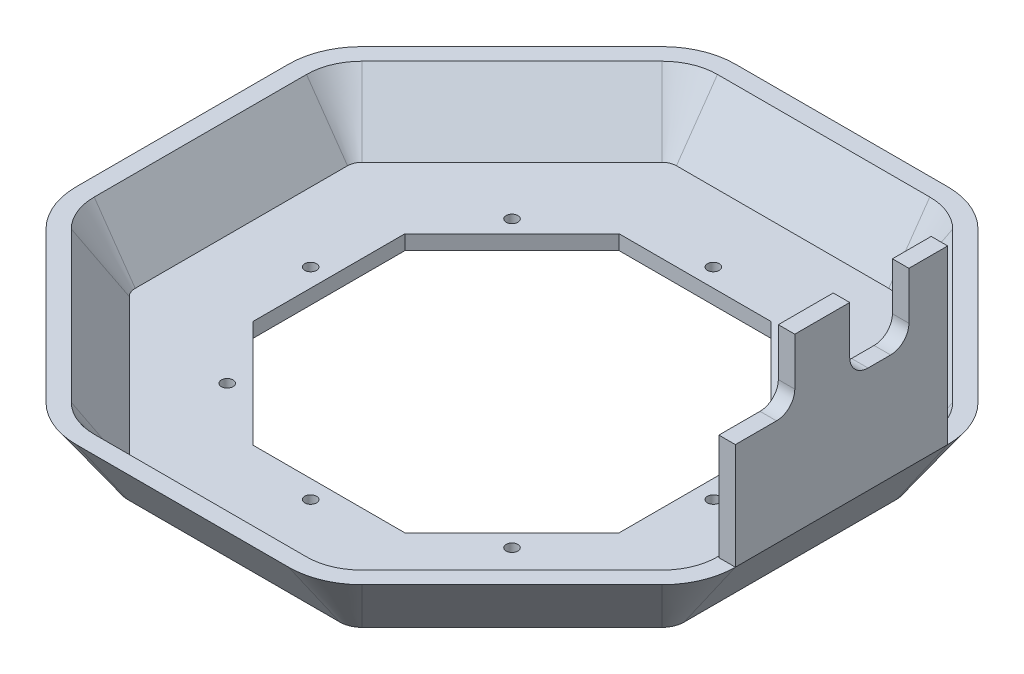
SolidWorks part; units mm, degrees
ref_plane "Front Plane" through (0, 0, 0) normal (0, 0, 1) x (1, 0, 0)
ref_plane "Top Plane" through (0, 0, 0) normal (0, 1, 0) x (1, 0, 0)
ref_plane "Right Plane" through (0, 0, 0) normal (1, 0, 0) x (0, 0, -1)
sketch "Sketch1" plane through (0, 0, 0) normal (0, 1, 0) x (1, 0, 0)
  line L1 (90, -28.9949) -> (90, 28.9949)
  line L2 (84.1421, 43.1371) -> (43.1371, 84.1421)
  line L3 (28.9949, 90) -> (-28.9949, 90)
  line L4 (-43.1371, 84.1421) -> (-84.1421, 43.1371)
  line L5 (-90, 28.9949) -> (-90, -28.9949)
  line L6 (-84.1421, -43.1371) -> (-43.1371, -84.1421)
  line L7 (-28.9949, -90) -> (28.9949, -90)
  line L8 (43.1371, -84.1421) -> (84.1421, -43.1371)
  circle A0 centre (0, 0) radius 90 construction
  arc A1 (-90, -28.9949) -> (-84.1421, -43.1371) centre (-70, -28.9949) ccw
  arc A2 (-43.1371, -84.1421) -> (-28.9949, -90) centre (-28.9949, -70) ccw
  arc A3 (28.9949, -90) -> (43.1371, -84.1421) centre (28.9949, -70) ccw
  arc A4 (90, -28.9949) -> (84.1421, -43.1371) centre (70, -28.9949) cw
  arc A5 (90, 28.9949) -> (84.1421, 43.1371) centre (70, 28.9949) ccw
  arc A6 (43.1371, 84.1421) -> (28.9949, 90) centre (28.9949, 70) ccw
  arc A7 (-28.9949, 90) -> (-43.1371, 84.1421) centre (-28.9949, 70) ccw
  arc A8 (-84.1421, 43.1371) -> (-90, 28.9949) centre (-70, 28.9949) ccw
  dimension "D1" = 180
  dimension "D2" = 20
extrude "Initial extrude" add sketch "Sketch1" along normal blind 20
chamfer "Top chamfer" distance 20 angle 35 16 edges at (0, 20, 90) (-63.6396, 20, 63.6396) (-90, 20, 0) (-63.6396, 20, -63.6396) (0, 20, -90) (63.6396, 20, -63.6396) (90, 20, 0) (63.6396, 20, 63.6396) (-88.4776, 20, -36.6486) (-36.6486, 20, -88.4776) (36.6486, 20, -88.4776) (88.4776, 20, -36.6486) (88.4776, 20, 36.6486) (36.6486, 20, 88.4776) (-36.6486, 20, 88.4776) (-88.4776, 20, 36.6486) first distance on face at (0, 10, 90) first distance on face at (-63.6396, 10, 63.6396) first distance on face at (-90, 10, 0) first distance on face at (-63.6396, 10, -63.6396) first distance on face at (0, 10, -90) first distance on face at (63.6396, 10, -63.6396) first distance on face at (90, 10, 0) first distance on face at (63.6396, 10, 63.6396) first distance on face at (-87.7743, 10, -36.3573) first distance on face at (-36.3573, 10, -87.7743) first distance on face at (36.3573, 10, -87.7743) first distance on face at (87.7743, 10, -36.3573) first distance on face at (87.7743, 10, 36.3573) first distance on face at (36.3573, 10, 87.7743) first distance on face at (-36.3573, 10, 87.7743) first distance on face at (-87.7743, 10, 36.3573)
shell "Top shell" thickness 4 removed face at (0, 0, 0)
sketch "Sketch2" plane through (0, 20, 0) normal (0, 1, 0) x (1, 0, 0)
  line L1 (20.7107, 50) -> (-20.7107, 50)
  line L2 (-20.7107, 50) -> (-50, 20.7107)
  line L3 (-50, 20.7107) -> (-50, -20.7107)
  line L4 (-50, -20.7107) -> (-20.7107, -50)
  line L5 (-20.7107, -50) -> (20.7107, -50)
  line L6 (20.7107, -50) -> (50, -20.7107)
  line L7 (50, -20.7107) -> (50, 20.7107)
  line L8 (50, 20.7107) -> (20.7107, 50)
  circle A0 centre (0, 0) radius 50 construction
  dimension "D1" = 100
extrude "Interior hex hole" cut sketch "Sketch2" against normal through all
sketch "Sketch3" plane through (0, 16, 0) normal (0, -1, 0) x (1, 0, 0)
  line L0 (-50, -20.7107) -> (-50, 20.7107) construction
  circle A0 centre (-55, 0) radius 1.6
  circle A1 centre (-38.8909, 38.8909) radius 1.6
  circle A2 centre (0, 55) radius 1.6
  circle A3 centre (38.8909, 38.8909) radius 1.6
  circle A4 centre (55, 0) radius 1.6
  circle A5 centre (38.8909, -38.8909) radius 1.6
  circle A6 centre (0, -55) radius 1.6
  circle A7 centre (-38.8909, -38.8909) radius 1.6
  point P22 (0, 0)
  dimension "D1" = 3.2
  dimension "D2" = 5
  dimension "D3" = 8
extrude "Top screw holes" cut sketch "Sketch3" against normal through all
ref_plane "Plane1" through (0, 0, 0) normal (0, 0, -1) x (-1, 0, 0)
sketch "Sketch6" plane through (0, 0, 0) normal (0, -1, 0) x (1, 0, 0)
  line L0 (-90, -28.9949) -> (-90, 28.9949) construction
  line L1 (-90, -28.9949) -> (-85.5, -28.9949)
  line L2 (-90, -28.9949) -> (-90, 28.9949)
  line L3 (-90, 28.9949) -> (-85.5, 28.9949)
  line L4 (-85.5, -28.9949) -> (-85.5, 28.9949)
  dimension "D1" = 4.5
extrude "Boss-Extrude2" add sketch "Sketch6" along normal blind 29
sketch "Sketch7" plane through (0, -29, 0) normal (0, -1, 0) x (1, 0, 0)
  line L0 (-90, 28.9949) -> (-90, -28.9949) construction
  line L1 (-90, -2.2382) -> (-85.5, -2.2382)
  line L2 (-90, -2.2382) -> (-90, 12.7618)
  line L3 (-90, 12.7618) -> (-85.5, 12.7618)
  line L4 (-85.5, -2.2382) -> (-85.5, 12.7618)
  line L6 (-85.5, -28.9949) -> (-85.5, 28.9949) construction
  line L8 (-90, -18.4069) -> (-85.5, -18.4069)
  line L9 (-90, -18.4069) -> (-90, -28.9949)
  line L10 (-90, -28.9949) -> (-85.5, -28.9949)
  line L11 (-85.5, -18.4069) -> (-85.5, -28.9949)
  line L12 (-84.1603, -16.3069) -> (-90.5103, -16.3069) construction
  line L13 (-87.5639, -4.3054) -> (-90.5103, -4.3054) construction
  line M3 (-90, 28.9949) -> (-90, -28.9949)
  line M4 (-90, -28.9949) -> (-85.5, -28.9949)
  line M5 (-85.5, -28.9949) -> (-85.5, 28.9949)
  dimension "D1" = 15
  dimension "D2" = 2.1
  dimension "D3" = 2.0672
extrude "Boss-Extrude3" add sketch "Sketch7" along normal blind 18 contours L8 M3 M4 M5 | L3 L4 L1 L2 region at (-87.75, -29, -23.7009)
ref_plane "Plane2" through (0, 0, 0) normal (0, -1, 0) x (-1, 0, 0)
fillet "Fillet1" radius 5 3 edges at (-87.75, -29, 12.7618) (-87.75, -29, -2.2382) (-87.75, -29, -18.4069)
move or copy body "Body-Move/Copy1" bodies to move or copy 109 copy no rotation origin (0, -13.5, 0) rotation axis (0, 0, 1) rotation angle 180
